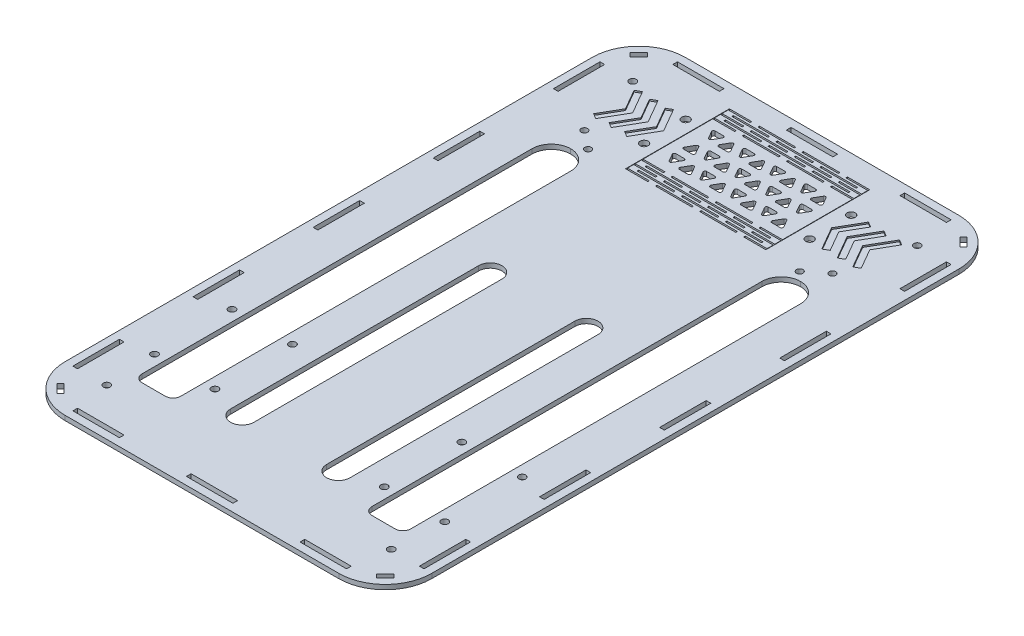
SolidWorks part; units mm, degrees
ref_plane "Front Plane" through (0, 0, 0) normal (0, 0, 1) x (1, 0, 0)
ref_plane "Top Plane" through (0, 0, 0) normal (0, 1, 0) x (1, 0, 0)
ref_plane "Right Plane" through (0, 0, 0) normal (1, 0, 0) x (0, 0, -1)
sketch "Sketch1" plane through (0, 0, 0) normal (0, 1, 0) x (1, 0, 0)
  line L1 (-118.25, -200) -> (118.25, -200)
  line L2 (-118.25, -200) -> (-118.25, 200)
  line L3 (-118.25, 200) -> (118.25, 200)
  line L4 (118.25, -200) -> (118.25, 200)
  line L5 (-118.25, -200) -> (118.25, 200) construction
  line L6 (-118.25, 200) -> (118.25, -200) construction
  point P0 (0, 0)
  dimension "D1" = 400
  dimension "D2" = 236.5
extrude "Boss-Extrude1" add sketch "Sketch1" along normal mid plane 3
fillet "Fillet1" radius 30 4 edges at (-118.25, 0, 200) (-118.25, 0, -200) (118.25, 0, -200) (118.25, 0, 200)
sketch "Sketch2" plane through (0, 1.5, 0) normal (0, 1, 0) x (1, 0, 0)
  line L0 (-118.25, 170) -> (-118.25, -170) construction
  line L1 (-113.25, -170) -> (-110.25, -170)
  line L2 (-113.25, -170) -> (-113.25, -140)
  line L3 (-113.25, -140) -> (-110.25, -140)
  line L4 (-110.25, -170) -> (-110.25, -140)
  line L5 (-113.25, -92.5) -> (-113.25, -62.5)
  line L6 (-113.25, -92.5) -> (-110.25, -92.5)
  line L7 (-110.25, -92.5) -> (-110.25, -62.5)
  line L8 (-113.25, -62.5) -> (-110.25, -62.5)
  line L9 (-113.25, -15) -> (-113.25, 15)
  line L10 (-113.25, -15) -> (-110.25, -15)
  line L11 (-110.25, -15) -> (-110.25, 15)
  line L12 (-113.25, 15) -> (-110.25, 15)
  line L13 (-113.25, 62.5) -> (-113.25, 92.5)
  line L14 (-113.25, 62.5) -> (-110.25, 62.5)
  line L15 (-110.25, 62.5) -> (-110.25, 92.5)
  line L16 (-113.25, 92.5) -> (-110.25, 92.5)
  line L17 (-113.25, 140) -> (-113.25, 170)
  line L18 (-113.25, 140) -> (-110.25, 140)
  line L19 (-110.25, 140) -> (-110.25, 170)
  line L20 (-113.25, 170) -> (-110.25, 170)
  dimension "D1" = 3
  dimension "D2" = 5
  dimension "D3" = 30
  dimension "D4" = 5
extrude "Cut-Extrude1" cut sketch "Sketch2" against normal through all
sketch "Sketch3" plane through (0, 1.5, 0) normal (0, 1, 0) x (1, 0, 0)
  line L0 (-110.25, 170) -> (-113.25, 170) construction
  line L1 (-88.25, 195) -> (-58.25, 195)
  line L2 (-88.25, 195) -> (-88.25, 192)
  line L3 (-88.25, 192) -> (-58.25, 192)
  line L4 (-58.25, 195) -> (-58.25, 192)
  line L5 (-110.25, 140) -> (-110.25, 170) construction
  line L6 (-113.25, 170) -> (-118.25, 170) construction
  line L7 (-88.25, 195) -> (-88.25, 200) construction
  line L8 (-15, 195) -> (-15, 192)
  line L9 (-15, 195) -> (15, 195)
  line L10 (15, 195) -> (15, 192)
  line L11 (-15, 192) -> (15, 192)
  line L12 (58.25, 195) -> (58.25, 192)
  line L13 (58.25, 195) -> (88.25, 195)
  line L14 (88.25, 195) -> (88.25, 192)
  line L15 (58.25, 192) -> (88.25, 192)
  dimension "D1" = 3
extrude "Cut-Extrude2" cut sketch "Sketch3" against normal through all
mirror "Mirror1" about plane through (0, 0, 0) normal (0, 0, 1) of "Cut-Extrude2"
mirror "Mirror2" about plane through (0, 0, 0) normal (1, 0, 0) of "Cut-Extrude1"
sketch "Sketch4" plane through (0, 1.5, 0) normal (0, 1, 0) x (1, 0, 0)
  line L0 (-103.8063, 185.5563) -> (-105.9277, 187.6777) construction
  line L1 (-108.7561, 184.8492) -> (-103.0992, 190.5061)
  line L2 (-103.0992, 190.5061) -> (-100.7186, 188.1255)
  line L3 (-100.7186, 188.1255) -> (-106.3755, 182.4686)
  line L4 (-106.3755, 182.4686) -> (-108.7561, 184.8492)
  line L5 (0, 200) -> (0, -200) construction
  line L6 (88.25, 200) -> (-88.25, 200) construction
  line L7 (-88.25, -200) -> (88.25, -200) construction
  line L8 (118.25, 0) -> (-118.25, 0) construction
  line L9 (118.25, -170) -> (118.25, 170) construction
  line L10 (-118.25, 170) -> (-118.25, -170) construction
  line L11 (100.7186, 188.1255) -> (106.3755, 182.4686)
  line L12 (103.0992, 190.5061) -> (100.7186, 188.1255)
  line L13 (108.7561, 184.8492) -> (103.0992, 190.5061)
  line L14 (106.3755, 182.4686) -> (108.7561, 184.8492)
  line L15 (103.0992, -190.5061) -> (100.7186, -188.1255)
  line L16 (108.7561, -184.8492) -> (103.0992, -190.5061)
  line L17 (106.3755, -182.4686) -> (108.7561, -184.8492)
  line L18 (100.7186, -188.1255) -> (106.3755, -182.4686)
  line L19 (-100.7186, -188.1255) -> (-106.3755, -182.4686)
  line L20 (-103.0992, -190.5061) -> (-100.7186, -188.1255)
  line L21 (-108.7561, -184.8492) -> (-103.0992, -190.5061)
  line L22 (-106.3755, -182.4686) -> (-108.7561, -184.8492)
  arc A0 (-88.25, 192) -> (-110.25, 170) centre (-88.25, 170) ccw construction
  arc A1 (-88.25, 195) -> (-113.25, 170) centre (-88.25, 170) ccw construction
  arc A2 (-88.25, 200) -> (-118.25, 170) centre (-88.25, 170) ccw construction
  point P17 (-105.9277, 187.6777)
  dimension "D1" = 8
extrude "Cut-Extrude3" cut sketch "Sketch4" against normal through all
sketch "Sketch5" plane through (0, 1.5, 0) normal (0, 1, 0) x (1, 0, 0)
  line L0 (-74.1335, 26) -> (-74.1335, -152) construction
  line L1 (-92.3561, 26) -> (-55.9109, 26) construction
  line L2 (-92.3561, -152) -> (-55.9109, -152) construction
  line L3 (-48.8835, -134) -> (-99.3835, -134) construction
  line L4 (-48.8835, -134) -> (-99.3835, -134) construction
  line L5 (0, 0) -> (0, -200) construction
  line L6 (-88.25, -200) -> (88.25, -200) construction
  line L7 (48.8835, -134) -> (99.3835, -134) construction
  line L8 (74.1335, 26) -> (74.1335, -152) construction
  point P9 (-74.1335, -134)
sketch "Sketch6" plane through (0, 1.5, 0) normal (0, 1, 0) x (1, 0, 0)
  line L0 (-74.1335, 26) -> (-74.1335, -152) construction
  line L1 (-61.6335, 112) -> (-86.6335, 112)
  line L2 (-61.6335, 112) -> (-61.6335, -157)
  line L3 (-61.6335, -157) -> (-86.6335, -157)
  line L4 (-86.6335, 112) -> (-86.6335, -157)
  line L5 (-88.25, 192) -> (-58.25, 192) construction
  line L6 (-88.25, -192) -> (-58.25, -192) construction
  line L7 (0, 0) -> (0, -200) construction
  line L8 (0, 0) -> (0, -200) construction
  line L9 (86.6335, 112) -> (86.6335, -157)
  line L10 (61.6335, -157) -> (86.6335, -157)
  line L11 (61.6335, 112) -> (61.6335, -157)
  line L12 (61.6335, 112) -> (86.6335, 112)
  point P4 (-74.1335, -157)
  dimension "D1" = 25
  dimension "D2" = 80
  dimension "D3" = 35
extrude "Cut-Extrude4" cut sketch "Sketch6" against normal through all
sketch "Sketch7" plane through (0, 1.5, 0) normal (0, 1, 0) x (1, 0, 0)
  line L0 (-15, 192) -> (15, 192) construction
  line L1 (-60, 172) -> (60, 172) construction
  line L2 (-60, 172) -> (-60, 132) construction
  line L3 (-60, 132) -> (60, 132) construction
  line L4 (60, 172) -> (60, 132) construction
  line L5 (-60, 152) -> (60, 152) construction
  line L6 (0, 172) -> (0, 132) construction
  line L7 (-53.4, 165.4) -> (-53.4, 138.6) construction
  line L8 (-53.4, 138.6) -> (53.4, 138.6) construction
  line L9 (53.4, 138.6) -> (53.4, 165.4) construction
  line L10 (53.4, 165.4) -> (-53.4, 165.4) construction
  circle A0 centre (-53.4, 165.4) radius 2.6
  circle A1 centre (-53.4, 138.6) radius 2.6
  circle A2 centre (53.4, 138.6) radius 2.6
  circle A3 centre (53.4, 165.4) radius 2.6
  point P4 (0, 132)
  point P20 (0, 165.4)
  point P21 (-53.4, 152)
  dimension "D4" = 5.2
  dimension "D1" = 120
  dimension "D2" = 40
  dimension "D3" = 20
  dimension "D5" = 26.8
  dimension "D6" = 106.8
sketch "Sketch8" plane through (0, 1.5, 0) normal (0, 1, 0) x (1, 0, 0)
  line L0 (-45, 185.5) -> (-45, 118.5)
  line L1 (-45, 185.5) -> (45, 185.5) construction
  line L2 (45, 185.5) -> (45, 118.5)
  line L3 (0, 185.5) -> (0, 172) construction
  line L4 (-60, 172) -> (60, 172) construction
  line L5 (0, 132) -> (0, 118.5) construction
  line L6 (-60, 132) -> (60, 132) construction
  line L8 (45, 185.5) -> (45.25, 185.5)
  line L9 (45.25, 185.5) -> (45.25, 118.5)
  line L10 (45.25, 118.5) -> (45, 118.5)
  line L11 (-45.25, 118.5) -> (-45, 118.5)
  line L12 (-45.25, 185.5) -> (-45.25, 118.5)
  line L13 (-45, 185.5) -> (-45.25, 185.5)
  point P2 (0, 185.5)
  dimension "D1" = 90
  dimension "D2" = 67
  dimension "D3" = 0.25
extrude "Cut-Extrude5" cut sketch "Sketch8" against normal through all
sketch "Sketch9" plane through (0, 1.5, 0) normal (0, 1, 0) x (1, 0, 0)
  line L0 (-60, 172) -> (60, 172) construction
  line L1 (-40.25, 177) -> (-16.8333, 177)
  line L2 (-40.25, 177) -> (-40.25, 178)
  line L3 (-40.25, 172) -> (-16.8333, 172)
  line L4 (-40.25, 172) -> (-40.25, 173)
  line L5 (-40.25, 173) -> (-16.8333, 173)
  line L6 (-16.8333, 172) -> (-16.8333, 173)
  line L7 (-45, 118.5) -> (-45, 185.5) construction
  line L8 (45, 185.5) -> (45, 118.5) construction
  line L9 (-11.8333, 173) -> (11.5833, 173)
  line L10 (-11.8333, 173) -> (-11.8333, 172)
  line L11 (-11.8333, 172) -> (11.5833, 172)
  line L12 (11.5833, 173) -> (11.5833, 172)
  line L13 (16.5833, 173) -> (40, 173)
  line L14 (16.5833, 173) -> (16.5833, 172)
  line L15 (16.5833, 172) -> (40, 172)
  line L16 (40, 173) -> (40, 172)
  line L17 (-16.8333, 172.5) -> (-11.8333, 172.5) construction
  line L18 (11.5833, 172.5) -> (16.5833, 172.5) construction
  line L19 (-30.9167, 175) -> (-25.9167, 175) construction
  line L20 (-25.9167, 174.5) -> (-2.5, 174.5)
  line L21 (-25.9167, 174.5) -> (-25.9167, 175.5)
  line L22 (-25.9167, 175.5) -> (-2.5, 175.5)
  line L23 (-2.5, 174.5) -> (-2.5, 175.5)
  line L24 (2.5, 175.5) -> (25.9167, 175.5)
  line L25 (2.5, 175.5) -> (2.5, 174.5)
  line L26 (2.5, 174.5) -> (25.9167, 174.5)
  line L27 (25.9167, 175.5) -> (25.9167, 174.5)
  line L28 (30.9167, 175.5) -> (45, 175.5)
  line L29 (30.9167, 175.5) -> (30.9167, 174.5)
  line L30 (30.9167, 174.5) -> (45, 174.5)
  line L31 (45, 175.5) -> (45, 174.5)
  line L32 (-45, 175.5) -> (-30.9167, 175.5)
  line L33 (-45, 175.5) -> (-45, 174.5)
  line L34 (-45, 174.5) -> (-30.9167, 174.5)
  line L35 (-30.9167, 175.5) -> (-30.9167, 174.5)
  line L36 (-2.5, 175) -> (2.5, 175) construction
  line L37 (25.9167, 175) -> (30.9167, 175) construction
  line L38 (40, 172.5) -> (45, 172.5) construction
  line L39 (-40.25, 172.5) -> (-45.25, 172.5) construction
  line L40 (-45.25, 185.5) -> (-45.25, 118.5) construction
  line L41 (-40.25, 178) -> (-16.8333, 178)
  line L42 (-16.8333, 177) -> (-16.8333, 178)
  line L43 (-11.8333, 178) -> (11.5833, 178)
  line L44 (-11.8333, 178) -> (-11.8333, 177)
  line L45 (-11.8333, 177) -> (11.5833, 177)
  line L46 (11.5833, 178) -> (11.5833, 177)
  line L47 (16.5833, 178) -> (40, 178)
  line L48 (16.5833, 178) -> (16.5833, 177)
  line L49 (16.5833, 177) -> (40, 177)
  line L50 (40, 178) -> (40, 177)
  line L51 (-25.9167, 179.5) -> (-2.5, 179.5)
  line L52 (-25.9167, 179.5) -> (-25.9167, 180.5)
  line L53 (-25.9167, 180.5) -> (-2.5, 180.5)
  line L54 (-2.5, 179.5) -> (-2.5, 180.5)
  line L55 (2.5, 180.5) -> (25.9167, 180.5)
  line L56 (2.5, 180.5) -> (2.5, 179.5)
  line L57 (2.5, 179.5) -> (25.9167, 179.5)
  line L58 (25.9167, 180.5) -> (25.9167, 179.5)
  line L59 (30.9167, 180.5) -> (45, 180.5)
  line L60 (30.9167, 180.5) -> (30.9167, 179.5)
  line L61 (30.9167, 179.5) -> (45, 179.5)
  line L62 (45, 180.5) -> (45, 179.5)
  line L63 (-45, 180.5) -> (-30.9167, 180.5)
  line L64 (-45, 180.5) -> (-45, 179.5)
  line L65 (-45, 179.5) -> (-30.9167, 179.5)
  line L66 (-30.9167, 180.5) -> (-30.9167, 179.5)
  line L67 (-16.8333, 177.5) -> (-11.8333, 177.5) construction
  line L68 (11.5833, 177.5) -> (16.5833, 177.5) construction
  line L69 (-30.9167, 180) -> (-25.9167, 180) construction
  line L70 (-2.5, 180) -> (2.5, 180) construction
  line L71 (25.9167, 180) -> (30.9167, 180) construction
  line L72 (40, 177.5) -> (45, 177.5) construction
  line L73 (-40.25, 177.5) -> (-45.25, 177.5) construction
  line L74 (-40.25, 182) -> (-16.8333, 182)
  line L75 (-40.25, 182) -> (-40.25, 183)
  line L76 (-40.25, 183) -> (-16.8333, 183)
  line L77 (-16.8333, 182) -> (-16.8333, 183)
  line L78 (-11.8333, 183) -> (11.5833, 183)
  line L79 (-11.8333, 183) -> (-11.8333, 182)
  line L80 (-11.8333, 182) -> (11.5833, 182)
  line L81 (11.5833, 183) -> (11.5833, 182)
  line L82 (16.5833, 183) -> (40, 183)
  line L83 (16.5833, 183) -> (16.5833, 182)
  line L84 (16.5833, 182) -> (40, 182)
  line L85 (40, 183) -> (40, 182)
  line L86 (-25.9167, 184.5) -> (-2.5, 184.5)
  line L87 (-25.9167, 184.5) -> (-25.9167, 185.5)
  line L88 (-25.9167, 185.5) -> (-2.5, 185.5)
  line L89 (-2.5, 184.5) -> (-2.5, 185.5)
  line L90 (2.5, 185.5) -> (25.9167, 185.5)
  line L91 (2.5, 185.5) -> (2.5, 184.5)
  line L92 (2.5, 184.5) -> (25.9167, 184.5)
  line L93 (25.9167, 185.5) -> (25.9167, 184.5)
  line L94 (30.9167, 185.5) -> (45, 185.5)
  line L95 (30.9167, 185.5) -> (30.9167, 184.5)
  line L96 (30.9167, 184.5) -> (45, 184.5)
  line L97 (45, 185.5) -> (45, 184.5)
  line L98 (-45, 185.5) -> (-30.9167, 185.5)
  line L99 (-45, 185.5) -> (-45, 184.5)
  line L100 (-45, 184.5) -> (-30.9167, 184.5)
  line L101 (-30.9167, 185.5) -> (-30.9167, 184.5)
  line L102 (-16.8333, 182.5) -> (-11.8333, 182.5) construction
  line L103 (11.5833, 182.5) -> (16.5833, 182.5) construction
  line L104 (-30.9167, 185) -> (-25.9167, 185) construction
  line L105 (-2.5, 185) -> (2.5, 185) construction
  line L106 (25.9167, 185) -> (30.9167, 185) construction
  line L107 (40, 182.5) -> (45, 182.5) construction
  line L108 (-40.25, 182.5) -> (-45.25, 182.5) construction
  line L144 (-25.9167, 189.5) -> (-2.5, 189.5) [skipped]
  line L145 (-25.9167, 189.5) -> (-25.9167, 190.5) [skipped]
  line L146 (-25.9167, 190.5) -> (-2.5, 190.5) [skipped]
  line L147 (-2.5, 189.5) -> (-2.5, 190.5) [skipped]
  line L148 (2.5, 190.5) -> (25.9167, 190.5) [skipped]
  line L149 (2.5, 190.5) -> (2.5, 189.5) [skipped]
  line L150 (2.5, 189.5) -> (25.9167, 189.5) [skipped]
  line L151 (25.9167, 190.5) -> (25.9167, 189.5) [skipped]
  line L152 (30.9167, 190.5) -> (45, 190.5) [skipped]
  line L153 (30.9167, 190.5) -> (30.9167, 189.5) [skipped]
  line L154 (30.9167, 189.5) -> (45, 189.5) [skipped]
  line L155 (45, 190.5) -> (45, 189.5) [skipped]
  line L156 (-45, 190.5) -> (-30.9167, 190.5) [skipped]
  line L157 (-45, 190.5) -> (-45, 189.5) [skipped]
  line L158 (-45, 189.5) -> (-30.9167, 189.5) [skipped]
  line L159 (-30.9167, 190.5) -> (-30.9167, 189.5) [skipped]
  line L160 (-30.9167, 190) -> (-25.9167, 190) construction
  line L161 (-2.5, 190) -> (2.5, 190) construction
  line L162 (25.9167, 190) -> (30.9167, 190) construction
  line L163 (-40.25, 187) -> (-16.8333, 187) [skipped]
  line L164 (-40.25, 187) -> (-40.25, 188) [skipped]
  line L165 (-40.25, 188) -> (-16.8333, 188) [skipped]
  line L166 (-16.8333, 187) -> (-16.8333, 188) [skipped]
  line L167 (-11.8333, 188) -> (11.5833, 188) [skipped]
  line L168 (-11.8333, 188) -> (-11.8333, 187) [skipped]
  line L169 (-11.8333, 187) -> (11.5833, 187) [skipped]
  line L170 (11.5833, 188) -> (11.5833, 187) [skipped]
  line L171 (16.5833, 188) -> (40, 188) [skipped]
  line L172 (16.5833, 188) -> (16.5833, 187) [skipped]
  line L173 (16.5833, 187) -> (40, 187) [skipped]
  line L174 (40, 188) -> (40, 187) [skipped]
  line L175 (-16.8333, 187.5) -> (-11.8333, 187.5) construction
  line L176 (11.5833, 187.5) -> (16.5833, 187.5) construction
  line L177 (40, 187.5) -> (45, 187.5) construction
  line L178 (-40.25, 187.5) -> (-45.25, 187.5) construction
  dimension "D1" = 5
  dimension "D2" = 1
  dimension "D3" = 1.5
  dimension "D4" = 4
extrude "Cut-Extrude6" cut sketch "Sketch9" against normal through all
extrude "Cut-Extrude7" cut sketch "Sketch7" against normal through all
ref_plane "Plane1" through (0, 0, -152) normal (0, 0, -1) x (-1, 0, 0)
mirror "Mirror3" about plane through (0, 0, -152) normal (0, 0, -1) of "Cut-Extrude6"
sketch "Sketch10" plane through (0, 1.5, 0) normal (0, 1, 0) x (1, 0, 0)
  line L0 (61.6335, 112) -> (68.277, 117.3148) construction
  line L1 (61.6335, 112) -> (86.6335, 112) construction
  line L2 (61.6335, 112) -> (61.6335, 132) construction
  line L3 (61.6335, 132) -> (86.6335, 132) construction
  line L4 (86.6335, 112) -> (86.6335, 132) construction
  line L5 (68.277, 117.3148) -> (79.99, 126.6852) construction
  line L6 (79.99, 126.6852) -> (86.6335, 132) construction
  line L7 (86.6335, -157) -> (86.6335, 112) construction
  line L8 (61.6335, 112) -> (61.6335, -157) construction
  line L9 (0, -1.65) -> (0, 1.65) construction
  circle A0 centre (68.277, 117.3148) radius 2.1
  circle A1 centre (79.99, 126.6852) radius 2.1
  circle A2 centre (-79.99, 126.6852) radius 2.1
  circle A3 centre (-68.277, 117.3148) radius 2.1
  dimension "D3" = 4.2
  dimension "D1" = 15
  dimension "D2" = 20
extrude "Cut-Extrude8" cut sketch "Sketch10" against normal through all
fillet "Fillet2" radius 12.5 4 edges at (-61.6335, 0, -112) (-86.6335, 0, -112) (61.6335, 0, -112) (86.6335, 0, -112)
fillet "Fillet3" radius 5 4 edges at (-61.6335, 0, 157) (-86.6335, 0, 157) (61.6335, 0, 157) (86.6335, 0, 157)
sketch "Sketch11" plane through (0, 1.5, 0) normal (0, 1, 0) x (1, 0, 0)
  line L0 (0, -1.65) -> (0, 1.65) construction
  line L1 (-1.65, 0) -> (1.65, 0) construction
  line L4 (-118.25, 170) -> (-118.25, -170)
  line L5 (-88.25, -200) -> (88.25, -200)
  line L6 (118.25, -170) -> (118.25, 170)
  line L7 (88.25, 200) -> (-88.25, 200)
  line L8 (-118.25, 170) -> (-118.25, -170) construction
  line L9 (-88.25, -200) -> (88.25, -200) construction
  line L10 (118.25, -170) -> (118.25, 170) construction
  line L11 (88.25, 200) -> (-88.25, 200) construction
  circle A0 centre (91.75, 169.6667) radius 3.2 construction
  circle A1 centre (91.75, 169.6667) radius 3.2 construction
  circle A2 centre (91.75, 169.6667) radius 2.25
  circle A3 centre (-91.75, 169.6667) radius 2.25
  arc A4 (-118.25, -170) -> (-88.25, -200) centre (-88.25, -170) ccw
  arc A5 (88.25, -200) -> (118.25, -170) centre (88.25, -170) ccw
  arc A6 (118.25, 170) -> (88.25, 200) centre (88.25, 170) ccw
  arc A7 (-88.25, 200) -> (-118.25, 170) centre (-88.25, 170) ccw
  arc A8 (-118.25, -170) -> (-88.25, -200) centre (-88.25, -170) ccw construction
  arc A9 (88.25, -200) -> (118.25, -170) centre (88.25, -170) ccw construction
  arc A10 (118.25, 170) -> (88.25, 200) centre (88.25, 170) ccw construction
  arc A11 (-88.25, 200) -> (-118.25, 170) centre (-88.25, 170) ccw construction
  circle A12 centre (91.75, -169.6667) radius 2.25
  circle A13 centre (-91.75, -169.6667) radius 2.25
  dimension "D2" = 4.5
  dimension "D1" = 0
extrude "Cut-Extrude10" cut sketch "Sketch11" against normal through all
sketch "Sketch12" plane through (0, 1.5, 0) normal (0, 1, 0) x (1, 0, 0)
  line L0 (-31.0005, 17) -> (-31.0005, -143) construction
  line L1 (-23.5005, 17) -> (-23.5005, -143)
  line L2 (-38.5005, 17) -> (-38.5005, -143)
  line L3 (-74.1335, 26) -> (-74.1335, -152) construction
  line L4 (0, -1.65) -> (0, 1.65) construction
  line L5 (31.0005, 17) -> (31.0005, -143) construction
  line L6 (23.5005, 17) -> (23.5005, -143)
  line L7 (38.5005, 17) -> (38.5005, -143)
  arc A0 (-23.5005, 17) -> (-38.5005, 17) centre (-31.0005, 17) ccw
  arc A1 (-38.5005, -143) -> (-23.5005, -143) centre (-31.0005, -143) ccw
  arc A2 (23.5005, 17) -> (38.5005, 17) centre (31.0005, 17) cw
  arc A3 (38.5005, -143) -> (23.5005, -143) centre (31.0005, -143) cw
  point P2 (-31.0005, -63)
  point P13 (-74.1335, -63)
  point P18 (31.0005, -63)
  dimension "D1" = 43.133
  dimension "D2" = 15
  dimension "D3" = 160
extrude "Cut-Extrude11" cut sketch "Sketch12" against normal through all
sketch "Sketch13" plane through (0, 1.5, 0) normal (0, 1, 0) x (1, 0, 0)
  line L1 (-40.25, 172) -> (40, 172)
  line L2 (-40.25, 172) -> (-40.25, 173)
  line L3 (-40.25, 173) -> (40, 173)
  line L4 (40, 172) -> (40, 173)
  line L5 (40, 132) -> (-40.25, 132)
  line L6 (40, 132) -> (40, 131)
  line L7 (40, 131) -> (-40.25, 131)
  line L8 (-40.25, 132) -> (-40.25, 131)
extrude "Boss-Extrude3" add sketch "Sketch13" against normal through all
sketch "Sketch14" plane through (0, 1.5, 0) normal (0, 1, 0) x (1, 0, 0)
  line L0 (-39.1686, 168.5) -> (-34.7422, 160.8333)
  line L1 (-34.7422, 160.8333) -> (-30.3159, 168.5)
  line L2 (-30.3159, 168.5) -> (-39.1686, 168.5)
  line L3 (-34.7422, 155.8333) -> (-39.1686, 148.1667)
  line L4 (-39.1686, 148.1667) -> (-30.3159, 148.1667)
  line L5 (-30.3159, 148.1667) -> (-34.7422, 155.8333)
  line L6 (-39.1686, 143.1667) -> (-34.7422, 135.5)
  line L7 (-34.7422, 135.5) -> (-30.3159, 143.1667)
  line L8 (-30.3159, 143.1667) -> (-39.1686, 143.1667)
  line L9 (-34.7422, 143.1667) -> (-34.7422, 148.1667) construction
  line L10 (-34.7422, 155.8333) -> (-34.7422, 160.8333) construction
  line L11 (-34.7422, 168.5) -> (-34.7422, 174.5) construction
  line L12 (-45, 174.5) -> (-30.9167, 174.5) construction
  line L13 (-34.7422, 135.5) -> (-34.7422, 129.5) construction
  line L14 (-45, 129.5) -> (-30.9167, 129.5) construction
  line L16 (-24.8159, 174.5) -> (-24.8159, 129.5) construction
  line L17 (-25.9167, 174.5) -> (-2.5, 174.5) construction
  line L18 (-25.9167, 129.5) -> (-2.5, 129.5) construction
  line L19 (-24.8159, 174.5) -> (-34.7422, 174.5) construction
  line L20 (-29.7791, 174.5) -> (-29.7791, 129.4943) construction
  line L21 (-24.8159, 155.8333) -> (-24.8159, 160.8333) construction
  line L22 (-24.8159, 143.1667) -> (-24.8159, 148.1667) construction
  line L32 (-45.25, 152) -> (45.25, 152) construction
  line L33 (-45.25, 185.5) -> (-45.25, 118.5) construction
  line L34 (45.25, 118.5) -> (45.25, 185.5) construction
  line L35 (-24.8159, 143.1667) -> (-29.2422, 135.5)
  line L36 (-20.3895, 135.5) -> (-24.8159, 143.1667)
  line L37 (-29.2422, 135.5) -> (-20.3895, 135.5)
  line L38 (-20.3895, 155.8333) -> (-29.2422, 155.8333)
  line L39 (-24.8159, 148.1667) -> (-20.3895, 155.8333)
  line L40 (-29.2422, 155.8333) -> (-24.8159, 148.1667)
  line L41 (-24.8159, 168.5) -> (-29.2422, 160.8333)
  line L42 (-20.3895, 160.8333) -> (-24.8159, 168.5)
  line L43 (-29.2422, 160.8333) -> (-20.3895, 160.8333)
  line L44 (-19.3159, 168.5) -> (-14.8895, 160.8333)
  line L45 (-14.8895, 160.8333) -> (-10.4632, 168.5)
  line L46 (-10.4632, 168.5) -> (-19.3159, 168.5)
  line L47 (-14.8895, 155.8333) -> (-19.3159, 148.1667)
  line L48 (-19.3159, 148.1667) -> (-10.4632, 148.1667)
  line L49 (-10.4632, 148.1667) -> (-14.8895, 155.8333)
  line L50 (-19.3159, 143.1667) -> (-14.8895, 135.5)
  line L51 (-14.8895, 135.5) -> (-10.4632, 143.1667)
  line L52 (-10.4632, 143.1667) -> (-19.3159, 143.1667)
  line L53 (-4.9632, 143.1667) -> (-9.3895, 135.5)
  line L54 (-0.5368, 135.5) -> (-4.9632, 143.1667)
  line L55 (-9.3895, 135.5) -> (-0.5368, 135.5)
  line L56 (-0.5368, 155.8333) -> (-9.3895, 155.8333)
  line L57 (-4.9632, 148.1667) -> (-0.5368, 155.8333)
  line L58 (-9.3895, 155.8333) -> (-4.9632, 148.1667)
  line L59 (-4.9632, 168.5) -> (-9.3895, 160.8333)
  line L60 (-0.5368, 160.8333) -> (-4.9632, 168.5)
  line L61 (-9.3895, 160.8333) -> (-0.5368, 160.8333)
  line L62 (-14.8895, 143.1667) -> (-14.8895, 148.1667) construction
  line L63 (-14.8895, 155.8333) -> (-14.8895, 160.8333) construction
  line L64 (-4.9632, 155.8333) -> (-4.9632, 160.8333) construction
  line L65 (-4.9632, 143.1667) -> (-4.9632, 148.1667) construction
  line L66 (0.5368, 168.5) -> (4.9632, 160.8333)
  line L67 (4.9632, 160.8333) -> (9.3895, 168.5)
  line L68 (9.3895, 168.5) -> (0.5368, 168.5)
  line L69 (4.9632, 155.8333) -> (0.5368, 148.1667)
  line L70 (0.5368, 148.1667) -> (9.3895, 148.1667)
  line L71 (9.3895, 148.1667) -> (4.9632, 155.8333)
  line L72 (0.5368, 143.1667) -> (4.9632, 135.5)
  line L73 (4.9632, 135.5) -> (9.3895, 143.1667)
  line L74 (9.3895, 143.1667) -> (0.5368, 143.1667)
  line L75 (14.8895, 143.1667) -> (10.4632, 135.5)
  line L76 (19.3159, 135.5) -> (14.8895, 143.1667)
  line L77 (10.4632, 135.5) -> (19.3159, 135.5)
  line L78 (19.3159, 155.8333) -> (10.4632, 155.8333)
  line L79 (14.8895, 148.1667) -> (19.3159, 155.8333)
  line L80 (10.4632, 155.8333) -> (14.8895, 148.1667)
  line L81 (14.8895, 168.5) -> (10.4632, 160.8333)
  line L82 (19.3159, 160.8333) -> (14.8895, 168.5)
  line L83 (10.4632, 160.8333) -> (19.3159, 160.8333)
  line L84 (4.9632, 143.1667) -> (4.9632, 148.1667) construction
  line L85 (4.9632, 155.8333) -> (4.9632, 160.8333) construction
  line L86 (14.8895, 155.8333) -> (14.8895, 160.8333) construction
  line L87 (14.8895, 143.1667) -> (14.8895, 148.1667) construction
  line L88 (20.3895, 168.5) -> (24.8159, 160.8333)
  line L89 (24.8159, 160.8333) -> (29.2422, 168.5)
  line L90 (29.2422, 168.5) -> (20.3895, 168.5)
  line L91 (24.8159, 155.8333) -> (20.3895, 148.1667)
  line L92 (20.3895, 148.1667) -> (29.2422, 148.1667)
  line L93 (29.2422, 148.1667) -> (24.8159, 155.8333)
  line L94 (20.3895, 143.1667) -> (24.8159, 135.5)
  line L95 (24.8159, 135.5) -> (29.2422, 143.1667)
  line L96 (29.2422, 143.1667) -> (20.3895, 143.1667)
  line L97 (34.7422, 143.1667) -> (30.3159, 135.5)
  line L98 (39.1686, 135.5) -> (34.7422, 143.1667)
  line L99 (30.3159, 135.5) -> (39.1686, 135.5)
  line L100 (39.1686, 155.8333) -> (30.3159, 155.8333)
  line L101 (34.7422, 148.1667) -> (39.1686, 155.8333)
  line L102 (30.3159, 155.8333) -> (34.7422, 148.1667)
  line L103 (34.7422, 168.5) -> (30.3159, 160.8333)
  line L104 (39.1686, 160.8333) -> (34.7422, 168.5)
  line L105 (30.3159, 160.8333) -> (39.1686, 160.8333)
  line L106 (24.8159, 143.1667) -> (24.8159, 148.1667) construction
  line L107 (24.8159, 155.8333) -> (24.8159, 160.8333) construction
  line L108 (34.7422, 155.8333) -> (34.7422, 160.8333) construction
  line L109 (34.7422, 143.1667) -> (34.7422, 148.1667) construction
  line L110 (-39.1686, 148.1667) -> (-45, 148.1667) construction
  line L111 (45, 160.8333) -> (39.1686, 160.8333) construction
  line L112 (45, 174.5) -> (45, 129.5) construction
  line L113 (-45, 129.5) -> (-45, 174.5) construction
  line L114 (-30.3159, 168.5) -> (-24.8159, 168.5) construction
  line L115 (-19.3159, 168.5) -> (-24.8159, 168.5) construction
  dimension "D1" = 5
  dimension "D2" = 6
  dimension "D4" = 5.5
  dimension "D5" = 4
extrude "Cut-Extrude12" cut sketch "Sketch14" against normal through all
fillet "Fillet4" radius 1 72 edges at (39.1686, 0, -160.8333) (30.3159, 0, -160.8333) (34.7422, 0, -168.5) (30.3159, 0, -155.8333) (39.1686, 0, -155.8333) (34.7422, 0, -148.1667) (39.1686, 0, -135.5) (30.3159, 0, -135.5) (34.7422, 0, -143.1667) (29.2422, 0, -143.1667) (24.8159, 0, -135.5) (20.3895, 0, -143.1667) (29.2422, 0, -148.1667) (20.3895, 0, -148.1667) (24.8159, 0, -155.8333) (29.2422, 0, -168.5) (24.8159, 0, -160.8333) (20.3895, 0, -168.5) (19.3159, 0, -160.8333) (10.4632, 0, -160.8333) (14.8895, 0, -168.5) (10.4632, 0, -155.8333) (19.3159, 0, -155.8333) (14.8895, 0, -148.1667) (19.3159, 0, -135.5) (10.4632, 0, -135.5) (14.8895, 0, -143.1667) (9.3895, 0, -143.1667) (4.9632, 0, -135.5) (0.5368, 0, -143.1667) (9.3895, 0, -148.1667) (0.5368, 0, -148.1667) (4.9632, 0, -155.8333) (9.3895, 0, -168.5) (4.9632, 0, -160.8333) (0.5368, 0, -168.5) (-0.5368, 0, -160.8333) (-9.3895, 0, -160.8333) (-4.9632, 0, -168.5) (-9.3895, 0, -155.8333) (-0.5368, 0, -155.8333) (-4.9632, 0, -148.1667) (-20.3895, 0, -160.8333) (-29.2422, 0, -160.8333) (-24.8159, 0, -168.5) (-0.5368, 0, -135.5) (-9.3895, 0, -135.5) (-4.9632, 0, -143.1667) (-10.4632, 0, -143.1667) (-14.8895, 0, -135.5) (-19.3159, 0, -143.1667) (-10.4632, 0, -148.1667) (-19.3159, 0, -148.1667) (-14.8895, 0, -155.8333) (-10.4632, 0, -168.5) (-14.8895, 0, -160.8333) (-19.3159, 0, -168.5) (-29.2422, 0, -155.8333) (-20.3895, 0, -155.8333) (-24.8159, 0, -148.1667) (-20.3895, 0, -135.5) (-29.2422, 0, -135.5) (-24.8159, 0, -143.1667) (-30.3159, 0, -143.1667) (-34.7422, 0, -135.5) (-39.1686, 0, -143.1667) (-30.3159, 0, -148.1667) (-39.1686, 0, -148.1667) (-34.7422, 0, -155.8333) (-34.7422, 0, -160.8333) (-30.3159, 0, -168.5) (-39.1686, 0, -168.5)
sketch "Sketch15" plane through (0, 1.5, 0) normal (0, 1, 0) x (1, 0, 0)
  line L0 (-81.6335, -157) -> (-66.6335, -157) construction
  line L1 (-93.6335, -137) -> (-54.6335, -137) construction
  line L2 (-93.6335, -137) -> (-93.6335, -87) construction
  line L3 (-93.6335, -87) -> (-54.6335, -87) construction
  line L4 (-54.6335, -137) -> (-54.6335, -87) construction
  line L5 (-93.6335, -137) -> (-54.6335, -87) construction
  line L6 (-93.6335, -87) -> (-54.6335, -137) construction
  line L7 (-61.6335, -152) -> (-61.6335, 99.5) construction
  circle A0 centre (-54.6335, -87) radius 2.25
  circle A1 centre (-93.6335, -87) radius 2.25
  circle A2 centre (-93.6335, -137) radius 2.25
  circle A3 centre (-54.6335, -137) radius 2.25
  point P0 (-74.1335, -112)
  point P13 (-74.1335, -157)
  dimension "D1" = 4.5
  dimension "D2" = 7
  dimension "D3" = 50
  dimension "D4" = 20
extrude "Cut-Extrude13" cut sketch "Sketch15" against normal through all
sketch "Sketch16" plane through (0, 1.5, 0) normal (0, 1, 0) x (1, 0, 0)
  line L0 (-62.8737, 167.0676) -> (-54.1744, 152)
  line L1 (-54.1744, 152) -> (-62.8737, 136.9324)
  line L2 (-62.8737, 136.9324) -> (-66.3378, 138.9324)
  line L3 (-66.3378, 138.9324) -> (-58.7932, 152)
  line L4 (-58.7932, 152) -> (-66.3378, 165.0676)
  line L5 (-66.3378, 165.0676) -> (-62.8737, 167.0676)
  line L6 (-45.25, 185.5) -> (-45.25, 118.5) construction
  line L7 (-72.8737, 167.0676) -> (-64.1744, 152)
  line L8 (-64.1744, 152) -> (-72.8737, 136.9324)
  line L9 (-72.8737, 136.9324) -> (-76.3378, 138.9324)
  line L10 (-76.3378, 138.9324) -> (-68.7932, 152)
  line L11 (-68.7932, 152) -> (-76.3378, 165.0676)
  line L12 (-76.3378, 165.0676) -> (-72.8737, 167.0676)
  line L13 (-82.8737, 167.0676) -> (-74.1744, 152)
  line L14 (-74.1744, 152) -> (-82.8737, 136.9324)
  line L15 (-82.8737, 136.9324) -> (-86.3378, 138.9324)
  line L16 (-86.3378, 138.9324) -> (-78.7932, 152)
  line L17 (-78.7932, 152) -> (-86.3378, 165.0676)
  line L18 (-86.3378, 165.0676) -> (-82.8737, 167.0676)
  point P7 (-45.25, 152)
  dimension "D1" = 120
  dimension "D2" = 4
  dimension "D3" = 3
extrude "Cut-Extrude14" cut sketch "Sketch16" against normal blind 1
mirror "Mirror4" about plane through (0, 0, 0) normal (1, 0, 0) of "Cut-Extrude14", "Cut-Extrude13"
